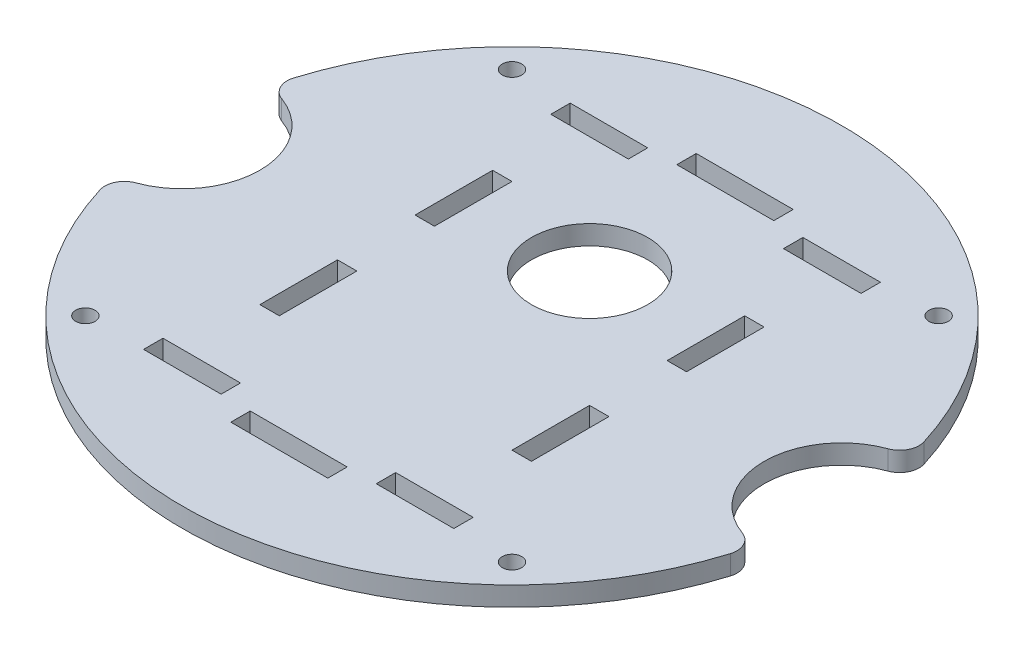
SolidWorks part; units mm, degrees
material "Pine"
ref_plane "Front Plane" through (0, 0, 0) normal (0, 0, 1) x (1, 0, 0)
ref_plane "Top Plane" through (0, 0, 0) normal (0, 1, 0) x (1, 0, 0)
ref_plane "Right Plane" through (0, 0, 0) normal (1, 0, 0) x (0, 0, -1)
sketch "Sketch1" plane through (0, 0, 0) normal (0, 1, 0) x (1, 0, 0)
  line L0 (0, 0) -> (0, 123.9148) construction
  line L1 (0, 0) -> (144.4711, 0) construction
  line L2 (-50.8, 63.5) -> (-25.4, 63.5)
  line L3 (-50.8, 63.5) -> (-50.8, 69.85)
  line L4 (-50.8, 69.85) -> (-25.4, 69.85)
  line L5 (-25.4, 63.5) -> (-25.4, 69.85)
  line L6 (25.4, 63.5) -> (25.4, 69.85)
  line L7 (50.8, 69.85) -> (25.4, 69.85)
  line L8 (50.8, 63.5) -> (50.8, 69.85)
  line L9 (50.8, 63.5) -> (25.4, 63.5)
  line L10 (-25.4, -63.5) -> (-25.4, -69.85)
  line L11 (-50.8, -63.5) -> (-25.4, -63.5)
  line L12 (-50.8, -63.5) -> (-50.8, -69.85)
  line L13 (-50.8, -69.85) -> (-25.4, -69.85)
  line L14 (50.8, -63.5) -> (50.8, -69.85)
  line L15 (50.8, -69.85) -> (25.4, -69.85)
  line L16 (25.4, -63.5) -> (25.4, -69.85)
  line L17 (50.8, -63.5) -> (25.4, -63.5)
  line L18 (38.1, -38.1) -> (44.45, -38.1)
  line L19 (38.1, 38.1) -> (44.45, 38.1)
  line L20 (38.1, 38.1) -> (38.1, 12.7)
  line L21 (38.1, 12.7) -> (44.45, 12.7)
  line L22 (44.45, 38.1) -> (44.45, 12.7)
  line L23 (38.1, -38.1) -> (38.1, -12.7)
  line L24 (38.1, -12.7) -> (44.45, -12.7)
  line L25 (44.45, -38.1) -> (44.45, -12.7)
  line L26 (-38.1, -38.1) -> (-44.45, -38.1)
  line L27 (-44.45, -38.1) -> (-44.45, -12.7)
  line L28 (-38.1, -38.1) -> (-38.1, -12.7)
  line L29 (-38.1, -12.7) -> (-44.45, -12.7)
  line L30 (-38.1, 12.7) -> (-44.45, 12.7)
  line L31 (-38.1, 38.1) -> (-38.1, 12.7)
  line L32 (-38.1, 38.1) -> (-44.45, 38.1)
  line L33 (-44.45, 38.1) -> (-44.45, 12.7)
  line L34 (-15.875, 69.85) -> (-15.875, 76.2)
  line L35 (15.875, -69.85) -> (-15.875, -69.85)
  line L36 (15.875, -69.85) -> (15.875, -76.2)
  line L37 (15.875, -76.2) -> (-15.875, -76.2)
  line L38 (-15.875, -69.85) -> (-15.875, -76.2)
  line L39 (15.875, -69.85) -> (-15.875, -76.2) construction
  line L40 (15.875, -76.2) -> (-15.875, -69.85) construction
  line L41 (15.875, 76.2) -> (-15.875, 76.2)
  line L42 (15.875, 69.85) -> (15.875, 76.2)
  line L43 (15.875, 69.85) -> (-15.875, 69.85)
  arc A0 (-103.1875, -31.7103) -> (103.1875, -31.7103) centre (0, 0) ccw
  circle A1 centre (0, 25.4) radius 19.05
  arc A2 (-99.2841, -23.876) -> (-99.2841, 23.876) centre (-107.95, 0) ccw
  arc A3 (-99.2841, 23.876) -> (-103.1875, 31.7103) centre (-97.1176, 29.845) cw
  arc A4 (-99.2841, -23.876) -> (-103.1875, -31.7103) centre (-97.1176, -29.845) ccw
  arc A5 (99.2841, -23.876) -> (103.1875, -31.7103) centre (97.1176, -29.845) cw
  arc A6 (99.2841, -23.876) -> (99.2841, 23.876) centre (107.95, 0) cw
  arc A7 (99.2841, 23.876) -> (103.1875, 31.7103) centre (97.1176, 29.845) ccw
  arc A8 (103.1875, 31.7103) -> (-103.1875, 31.7103) centre (0, 0) ccw
  point P52 (0, -73.025)
  dimension "D1" = 215.9
  dimension "D10" = 38.1
  dimension "D12" = 50.8
  dimension "D13" = 6.35
  dimension "D14" = 6.35
  dimension "D2" = 25.4
  dimension "D3" = 25.4
  dimension "D4" = 6.35
  dimension "D5" = 63.5
  dimension "D6" = 6.35
  dimension "D7" = 25.4
  dimension "D8" = 12.7
  dimension "D9" = 38.1
  dimension "D11" = 25.4
  dimension "D15" = 31.75
  dimension "D16" = 6.35
extrude "Boss-Extrude1" add sketch "Sketch1" along normal blind 6.35
sketch "Sketch2" plane through (0, 0, 0) normal (0, -1, 0) x (1, 0, 0)
  line L0 (0, 0) -> (0, 99.3828) construction
  line L1 (0, 0) -> (-150.0844, 0) construction
  circle A0 centre (-69.85, 69.85) radius 3.175
  circle A1 centre (69.85, 69.85) radius 3.175
  circle A2 centre (69.85, -69.85) radius 3.175
  circle A3 centre (-69.85, -69.85) radius 3.175
  dimension "D1" = 6.35
extrude "Cut-Extrude1" cut sketch "Sketch2" against normal up to surface (6.35 mm away) up to face at (0, 6.35, 73.025)
